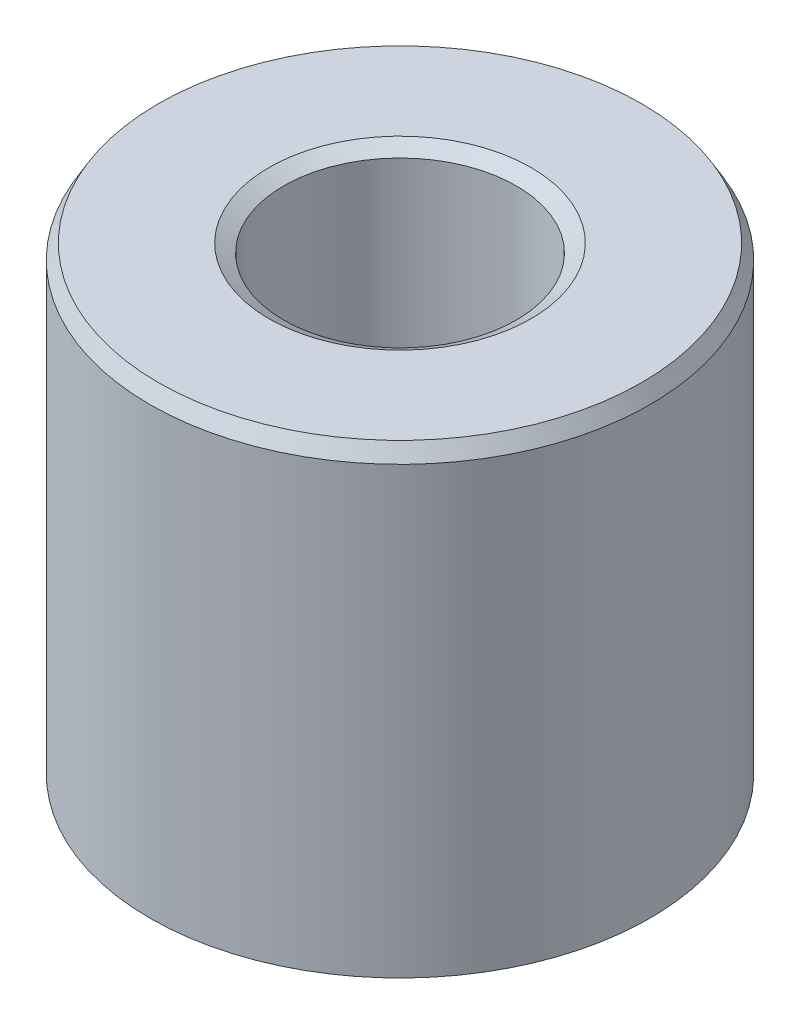
SolidWorks part; units mm, degrees
ref_plane "Front Plane" through (0, 0, 0) normal (0, 0, 1) x (1, 0, 0)
ref_plane "Top Plane" through (0, 0, 0) normal (0, 1, 0) x (1, 0, 0)
ref_plane "Right Plane" through (0, 0, 0) normal (1, 0, 0) x (0, 0, -1)
sketch "Sketch1" plane through (0, 0, 0) normal (0, 1, 0) x (1, 0, 0)
  circle A0 centre (0, 0) radius 40
  dimension "SLEEVE_OD" = 80
extrude "Boss-Extrude1" add sketch "Sketch1" along normal blind 74.8606
sketch "Sketch2" plane through (0, 0, 0) normal (0, 1, 0) x (1, 0, 0)
  circle A0 centre (0, 0) radius 18.6011
  dimension "BORE_D" = 37.2023
extrude "Cut-Extrude1" cut sketch "Sketch2" along normal through all
chamfer "Chamfer1" distance 2.3585 angle 30 4 edges at (0, 74.8606, 18.6011) (0, 0, 18.6011) (0, 0, 40) (0, 74.8606, 40) first distance on face at (0, 74.8606, 18.6011) first distance on face at (0, 0, 18.6011) first distance on face at (0, 74.8606, 40)
